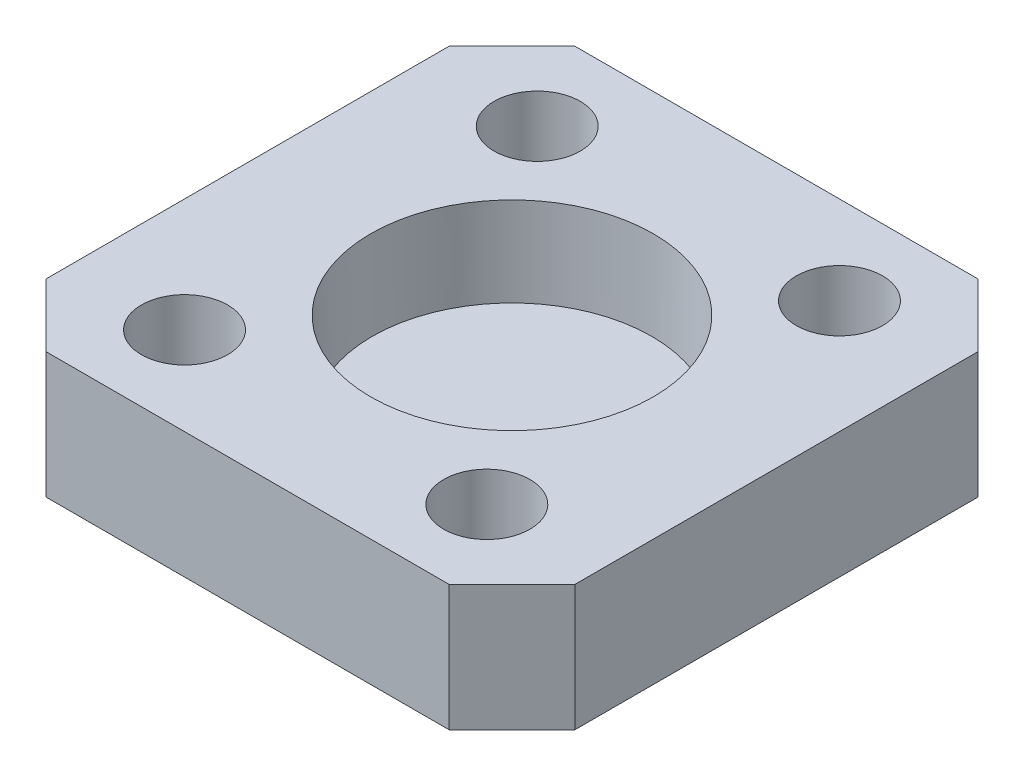
SolidWorks part; units mm, degrees
ref_plane "Front Plane" through (0, 0, 0) normal (0, 0, 1) x (1, 0, 0)
ref_plane "Top Plane" through (0, 0, 0) normal (0, 1, 0) x (1, 0, 0)
ref_plane "Right Plane" through (0, 0, 0) normal (1, 0, 0) x (0, 0, -1)
sketch "Sketch1" plane through (0, 0, 0) normal (0, 1, 0) x (1, 0, 0)
  line L1 (-21, -21) -> (21, -21)
  line L2 (-21, -21) -> (-21, 21)
  line L3 (-21, 21) -> (21, 21)
  line L4 (21, -21) -> (21, 21)
  line L5 (-21, -21) -> (21, 21) construction
  line L6 (-21, 21) -> (21, -21) construction
  point P0 (0, 0)
  dimension "D1" = 42
  dimension "D2" = 42
extrude "Boss-Extrude1" add sketch "Sketch1" along normal blind 10
sketch "Sketch2" plane through (0, 10, 0) normal (0, 1, 0) x (1, 0, 0)
  circle A0 centre (0, 0) radius 11.1
  dimension "D1" = 22.2
extrude "Cut-Extrude1" cut sketch "Sketch2" against normal blind 7
chamfer "Chamfer1" distance 7 angle 1 1 edges at (0, 10, 11.1) first distance on face at (0, 3, 11.1)
sketch "Sketch3" plane through (0, 10, 0) normal (0, 1, 0) x (1, 0, 0)
  line L0 (-21, 0) -> (21, 0) construction
  line L1 (-21, 21) -> (-21, -21) construction
  line L2 (21, -21) -> (21, 21) construction
  line L3 (0, 21) -> (0, -21) construction
  line L4 (21, 21) -> (-21, 21) construction
  line L5 (-21, -21) -> (21, -21) construction
  circle A0 centre (-12, 14) radius 3.425
  circle A7 centre (-12, -14) radius 3.425
  circle A8 centre (12, -14) radius 3.425
  circle A9 centre (12, 14) radius 3.425
  point P12 (0, 0)
  point P13 (0, 0)
  dimension "D1" = 6.85
  dimension "D2" = 12
  dimension "D3" = 14
extrude "Cut-Extrude2" cut sketch "Sketch3" against normal blind 8
chamfer "Chamfer2" distance 5 angle 45 4 edges at (-21, 5, 21) (21, 5, 21) (21, 5, -21) (-21, 5, -21)
sketch "Sketch4" plane through (0, 2, 0) normal (0, 1, 0) x (1, 0, 0)
  line L0 (-21, 0) -> (21, 0) construction
  line L1 (-21, 16) -> (-21, -16) construction
  line L2 (21, -16) -> (21, 16) construction
  line L3 (0, 21) -> (0, -21) construction
  line L4 (16, 21) -> (-16, 21) construction
  line L5 (-16, -21) -> (16, -21) construction
  circle A0 centre (-12, 14) radius 1.675
  circle A7 centre (12, 14) radius 1.675
  circle A8 centre (12, -14) radius 1.675
  circle A9 centre (-12, -14) radius 1.675
  dimension "D1" = 3.35
extrude "Cut-Extrude3" cut sketch "Sketch4" against normal up to next
